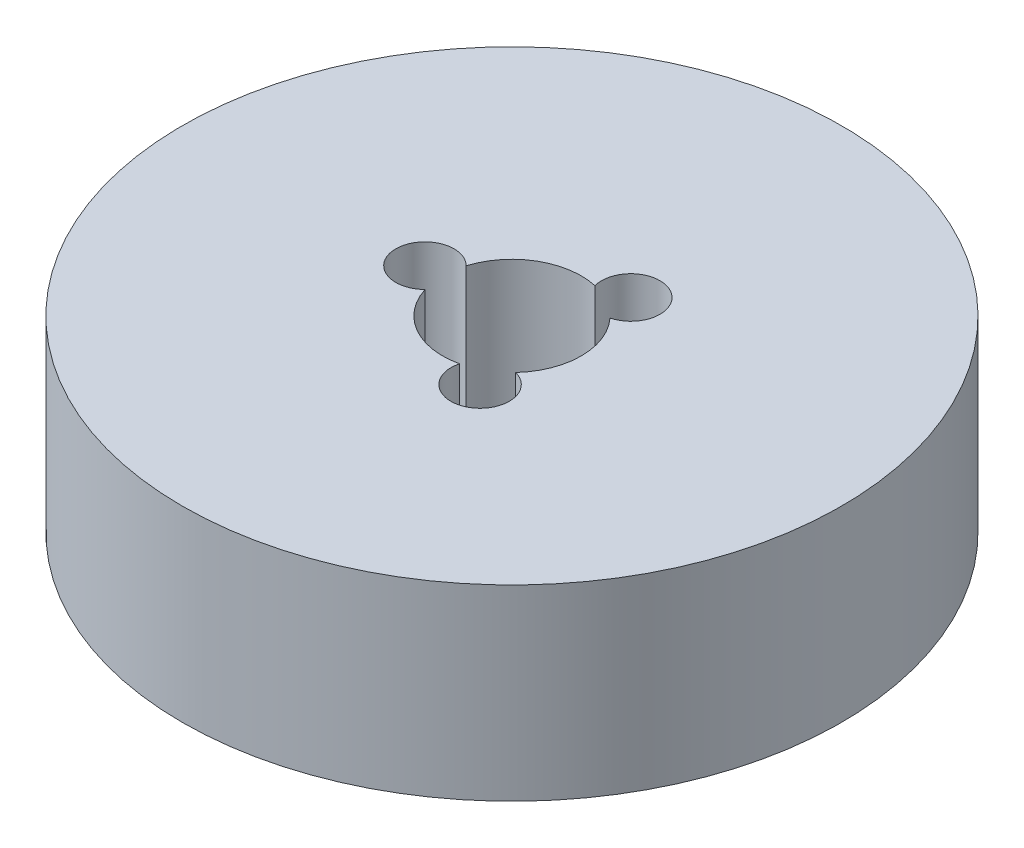
SolidWorks part; units mm, degrees
ref_plane "Front Plane" through (0, 0, 0) normal (0, 0, 1) x (1, 0, 0)
ref_plane "Top Plane" through (0, 0, 0) normal (0, 1, 0) x (1, 0, 0)
ref_plane "Right Plane" through (0, 0, 0) normal (1, 0, 0) x (0, 0, -1)
sketch "Sketch1" plane through (0, 0, 0) normal (0, 1, 0) x (1, 0, 0)
  circle A0 centre (0, 0) radius 47.5
  dimension "FLANGE_OD" = 95
extrude "Boss-Extrude1" add sketch "Sketch1" along normal blind 27
sketch "Sketch2" plane through (0, 0, 0) normal (0, 1, 0) x (1, 0, 0)
  circle A0 centre (0, 0) radius 10
  dimension "BORE_D" = 20
extrude "Cut-Extrude1" cut sketch "Sketch2" along normal through all
sketch "Sketch3" plane through (0, 27, 0) normal (0, 1, 0) x (1, 0, 0)
  circle A0 centre (0, 0) radius 12.541 construction
  circle A1 centre (-12.541, 0) radius 4.2039
  dimension "BOLT_D" = 8.4079
  dimension "BOLT_PCD" = 25.082
extrude "Cut-Extrude2" cut sketch "Sketch3" against normal blind 20.6681
pattern_circular "CirPattern1" count 3 over 360 about axis through (0, 0, 0) along (0, 1, 0) of "Cut-Extrude2"
